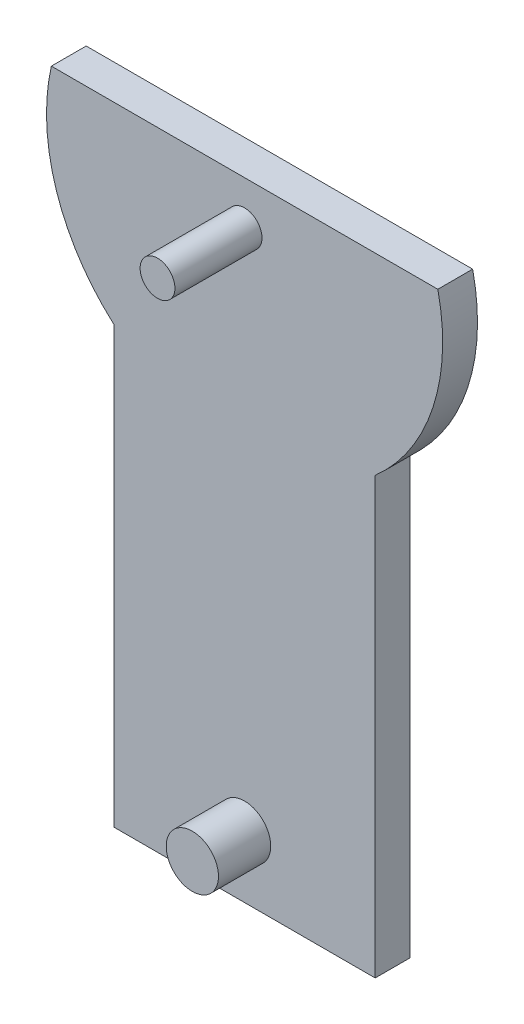
SolidWorks part; units mm, degrees
ref_plane "Front Plane" through (0, 0, 0) normal (0, 0, 1) x (1, 0, 0)
ref_plane "Top Plane" through (0, 0, 0) normal (0, 1, 0) x (1, 0, 0)
ref_plane "Right Plane" through (0, 0, 0) normal (1, 0, 0) x (0, 0, -1)
sketch "Sketch1" plane through (0, 0, 0) normal (0, 0, 1) x (1, 0, 0)
  line L0 (0, 150.6274) -> (0, -208.1955) construction
  line L1 (75, -335.5223) -> (75, -85.5223)
  line L2 (75, -335.5223) -> (-75, -335.5223)
  line L3 (-75, -335.5223) -> (-75, -85.5223)
  line L4 (-110.9687, 25) -> (110.9687, 25)
  arc A0 (-110.9687, 25) -> (110.9687, 25) centre (0, 0) ccw
  circle A1 centre (0, 0) radius 10
  point P10 (0, -335.5223)
  dimension "D1" = 227.5
  dimension "D2" = 20
  dimension "D3" = 25
  dimension "D4" = 250
  dimension "D5" = 150
extrude "Boss-Extrude1" add sketch "Sketch1" along normal blind 20 contours A0 L3 L2 L1 | L0 L4 A0 A1 | L4 L0 A1 A0 | L0 A1 | A1 L0 region at (50.6064, -35.5134, 0) region at (-50.6064, -35.5134, 0) region at (4.2441, 0, 0) region at (-4.2441, 0, 0) region at (0, -220.0462, 0)
extrude "Boss-Extrude2" add sketch "Sketch1<3>" along normal up to surface (50 mm away) from surface contours A1 starting at face at (0, -133.6618, 20)
sketch "Sketch1<3>" plane through (0, 0, 0) normal (0, 0, 1) x (1, 0, 0) same geometry as "Sketch1"
sketch "Sketch2" plane through (0, 0, 20) normal (0, 0, 1) x (1, 0, 0)
  circle A0 centre (0, -300) radius 15
  dimension "D2" = 30
  dimension "D1" = 300
extrude "Boss-Extrude3" add sketch "Sketch2" along normal blind 30
